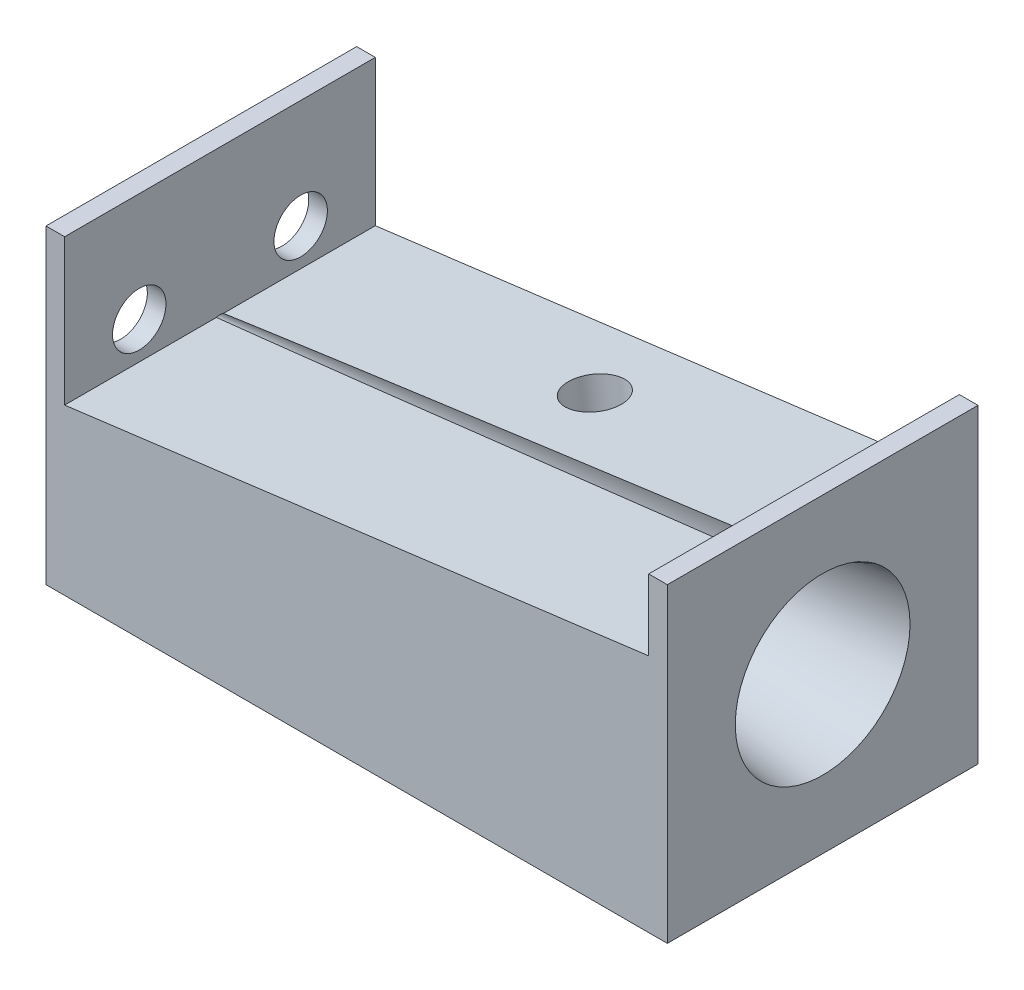
SolidWorks part; units mm, degrees
material "ABS"
ref_plane "Front Plane" through (0, 0, 0) normal (0, 0, 1) x (1, 0, 0)
ref_plane "Top Plane" through (0, 0, 0) normal (0, 1, 0) x (1, 0, 0)
ref_plane "Right Plane" through (0, 0, 0) normal (1, 0, 0) x (0, 0, -1)
sketch "Sketch1" plane through (0, 0, 0) normal (0, 1, 0) x (1, 0, 0)
  line L1 (-12.7, -6.35) -> (12.7, -6.35)
  line L2 (-12.7, -6.35) -> (-12.7, 6.35)
  line L3 (-12.7, 6.35) -> (12.7, 6.35)
  line L4 (12.7, -6.35) -> (12.7, 6.35)
  line L5 (-12.7, -6.35) -> (12.7, 6.35) construction
  line L6 (-12.7, 6.35) -> (12.7, -6.35) construction
  point P0 (0, 0)
  dimension "D1" = 25.4
  dimension "D2" = 12.7
extrude "Boss-Extrude1" add sketch "Sketch1" along normal blind 12.7
sketch "Sketch2" plane through (12.7, 0, 0) normal (1, 0, 0) x (0, 0, -1)
  line L0 (6.35, 12.7) -> (6.35, 0) construction
  line L1 (-6.35, 12.7) -> (6.35, 12.7) construction
  circle A1 centre (0, 6.35) radius 3.5719
  point P5 (6.35, 6.35)
  point P9 (0, 12.7)
  dimension "D1" = 7.1437
sketch "Sketch3" plane through (-12.7, 0, 0) normal (-1, 0, 0) x (0, 0, 1)
  line L0 (-6.35, 12.7) -> (-6.35, 0) construction
  line L1 (-6.35, 12.7) -> (6.35, 12.7) construction
  circle A1 centre (0, 6.35) radius 0.3175
  point P4 (-6.35, 6.35)
  point P7 (0, 12.7)
  dimension "D1" = 0.635
loft "Cut-Loft2" cut profiles "Sketch2", "Sketch3" connector at (12.7, 6.35, -3.5719) connector at (-12.7, 6.345, -0.3175)
ref_axis "Axis2" through (27.8977, 6.35, 0) along (-1, 0, 0)
sketch "Sketch6" plane through (0, 0, 6.35) normal (0, 0, 1) x (1, 0, 0)
  line L0 (-12.7, 12.7) -> (12.7, 12.7) construction
  line L1 (-11.938, 12.7) -> (11.938, 12.7)
  line L6 (11.938, 9.7986) -> (-11.938, 6.7395)
  line L7 (-11.938, 12.7) -> (-11.938, 6.7395)
  line L8 (11.938, 12.7) -> (11.938, 9.7986)
  line L9 (-12.7, 12.7) -> (-12.7, 0) construction
  line L10 (12.7, 12.7) -> (12.7, 0) construction
  line L11 (12.7, 9.9219) -> (-12.7, 6.6675) construction
  dimension "D1" = 0.762
  dimension "D2" = 0.762
  dimension "D3" = 0.0254
extrude "Cut-Extrude2" cut sketch "Sketch6" against normal up to surface (12.7 mm away) up to face at (0, 6.35, -6.35)
hole_wizard "#2-56 Tapped Hole2" positions "Sketch23" profile "Sketch24" tap size "#2-56" standard "ANSI Inch"
sketch "Sketch23" plane through (-1.0424, 8.1355, 0) normal (-0.1271, 0.9919, 0) x (0.9919, 0.1271, 0)
  line L0 (13.0865, 6.35) -> (-10.9847, 6.35) construction
  line L2 (13.0865, 6.35) -> (13.0865, 0.421) construction
  point P0 (1.0509, 3.3855)
  point P5 (1.0509, 6.35)
  point P11 (13.0865, 3.3855)
sketch "Sketch24" plane through (0, 8.2691, -3.3855) normal (0, 0, 1) x (-0.9919, -0.1271, 0)
  line L0 (0, 0) -> (0, 3.9583)
  line L1 (0, 3.9583) -> (1.0922, 3.302)
  line L2 (1.0922, 3.302) -> (1.0922, 0)
  line L5 (1.0922, 0) -> (0, 0)
  line L10 (0, 3.9583) -> (-1.0922, 3.302) construction
  line L11 (0, -6.35) -> (0, 107.95) construction
  dimension "Tap Drill Dia." = 2.1844
  dimension "Tap Drill Depth" = 3.302
  dimension "Drill Angle" = 118
cosmetic thread "Hole Thread2" parameters "D1"=2.794, "D2"=2.1844
hole_wizard "#2-56 Tapped Hole3" positions "Sketch25" profile "Sketch26" tap size "#2-56" standard "ANSI Inch"
sketch "Sketch25" plane through (-12.7, 0, 0) normal (-1, 0, 0) x (0, 0, 1)
  point P0 (0, 2.54)
  dimension "D1" = 3.81
sketch "Sketch26" plane through (-12.7, 2.54, 0) normal (0, 1, 0) x (0, 0, 1)
  line L0 (0, 0) -> (0, 3.9583)
  line L1 (0, 3.9583) -> (1.0922, 3.302)
  line L2 (1.0922, 3.302) -> (1.0922, 0)
  line L5 (1.0922, 0) -> (0, 0)
  line L10 (0, 3.9583) -> (-1.0922, 3.302) construction
  line L11 (0, -6.35) -> (0, 107.95) construction
  dimension "Tap Drill Dia." = 2.1844
  dimension "Tap Drill Depth" = 3.302
  dimension "Drill Angle" = 118
cosmetic thread "Hole Thread3" parameters "D1"=2.794, "D2"=2.1844
pattern_circular "CirPattern1" count 3 over 360 about axis through (27.8977, 6.35, 0) along (-1, 0, 0) of "#2-56 Tapped Hole3"
